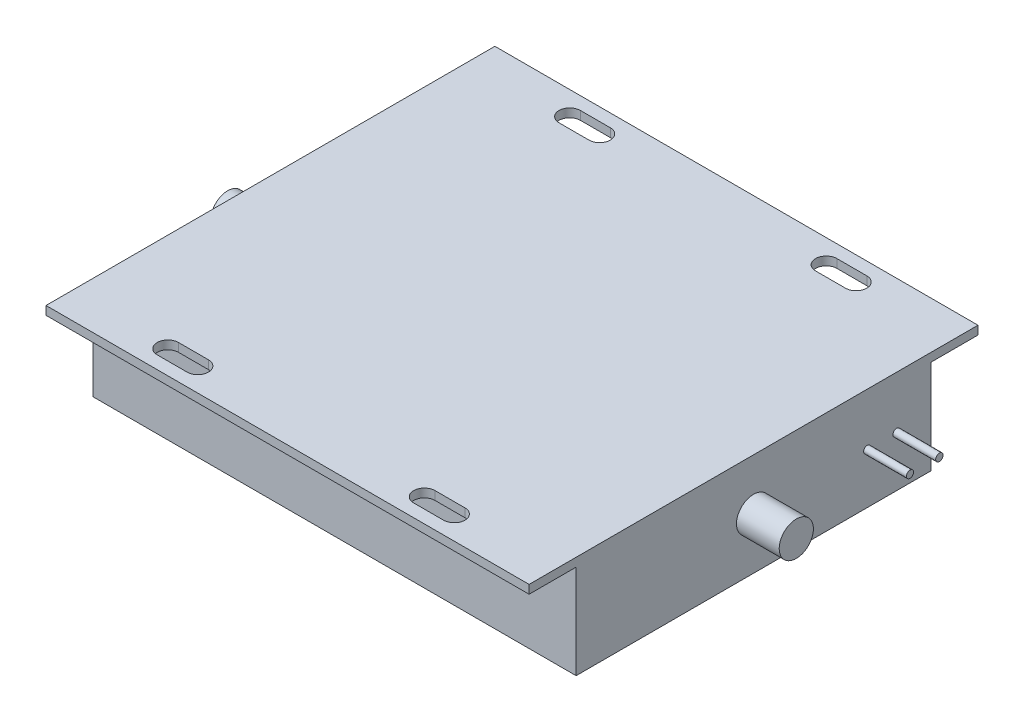
SolidWorks part; units mm, degrees
ref_plane "前基準面" through (0, 0, 0) normal (0, 0, 1) x (1, 0, 0)
ref_plane "上基準面" through (0, 0, 0) normal (0, 1, 0) x (1, 0, 0)
ref_plane "右基準面" through (0, 0, 0) normal (1, 0, 0) x (0, 0, -1)
ref_plane "平面1" through (0, 31, 0) normal (0, 1, 0) x (1, 0, 0)
sketch "草圖1" plane through (0, 31, 0) normal (0, 1, 0) x (1, 0, 0)
  line L0 (56.5, -41.5) -> (56.5, 41.5)
  line L1 (56.5, 41.5) -> (-56.5, 41.5)
  line L2 (-56.5, 41.5) -> (-56.5, -41.5)
  line L3 (-56.5, -41.5) -> (56.5, -41.5)
  line L4 (-56.5, 41.5) -> (56.5, -41.5) construction
  line L5 (56.5, 41.5) -> (-56.5, -41.5) construction
  point P4 (0, 0)
  dimension "D1" = 113
  dimension "D2" = 83
extrude "填料-伸長1" add sketch "草圖1" against normal blind 24
sketch "草圖21" plane through (0, 0, 0) normal (0, 0, -1) x (-1, 0, 0)
  line L0 (-56.5, 31) -> (56.5, 31)
  line L1 (56.5, 31) -> (56.5, 29)
  line L2 (56.5, 29) -> (-56.5, 29)
  line L3 (-56.5, 29) -> (-56.5, 31)
  line L4 (-56.5, 7) -> (-56.5, 31) construction
  line L5 (56.5, 7) -> (56.5, 31) construction
  line L6 (55, 31) -> (-55, 31) construction
  dimension "D1" = 2
extrude "填料-伸長2" add sketch "草圖21" along normal mid plane 105
sketch "草圖22" plane through (0, 31, 0) normal (0, 1, 0) x (-1, 0, 0)
  line L7 (0, 0) -> (0, -47) construction
  line L9 (32.5852, 0) -> (-22.6315, 0) construction
  line L10 (-26.5, -47) -> (-33.5, -47) construction
  line L11 (-26.5, -49.5) -> (-33.5, -49.5)
  line L12 (-26.5, -44.5) -> (-33.5, -44.5)
  arc A3 (-26.5, -49.5) -> (-26.5, -44.5) centre (-26.5, -47) ccw
  arc A4 (-33.5, -44.5) -> (-33.5, -49.5) centre (-33.5, -47) ccw
  point P16 (-30, -47)
  point P21 (-24, -47)
  point P22 (-36, -47)
  dimension "D5" = 12
  dimension "D6" = 5
  dimension "D7" = 72
  dimension "D8" = 94
extrude "除料-伸長20" cut sketch "草圖22" against normal through all contours L12 A4 L11 A3
mirror "鏡射1" about plane through (0, 0, 0) normal (1, 0, 0) of "除料-伸長20"
mirror "鏡射2" about plane through (0, 0, 0) normal (0, 0, 1) of "鏡射1"
sketch "草圖27" plane through (-56.5, 0, 0) normal (-1, 0, 0) x (0, 0, 1)
  line L1 (55, 31) -> (-55, 31) construction
  circle A0 centre (0, 19) radius 4
  dimension "D1" = 8
  dimension "D2" = 12
extrude "填料-伸長4" add sketch "草圖27" along normal blind 10
mirror "鏡射3" about plane through (0, 0, 0) normal (1, 0, 0) of "填料-伸長4"
other "連接點1" parameters "直徑"=25.4, "殘段長度"=38.1
ref_axis "基準軸1" through (76.5, 19, 0) along (-1, 0, 0)
other "連接點2" parameters "直徑"=25.4, "殘段長度"=38.1
ref_axis "基準軸2" through (-76.5, 19, 0) along (1, 0, 0)
sketch "草圖28" plane through (56.5, 0, 0) normal (1, 0, 0) x (0, 0, -1)
  circle A0 centre (26.5866, 18.7692) radius 0.8353
  circle A1 centre (33.4661, 18.7692) radius 0.8666
  point P4 (-29.7887, 18.7692)
  point P5 (-24.0751, 18.7692)
  point P6 (33.4661, 18.7692)
  point P7 (26.5866, 18.7692)
extrude "填料-伸長5" add sketch "草圖28" along normal blind 10
